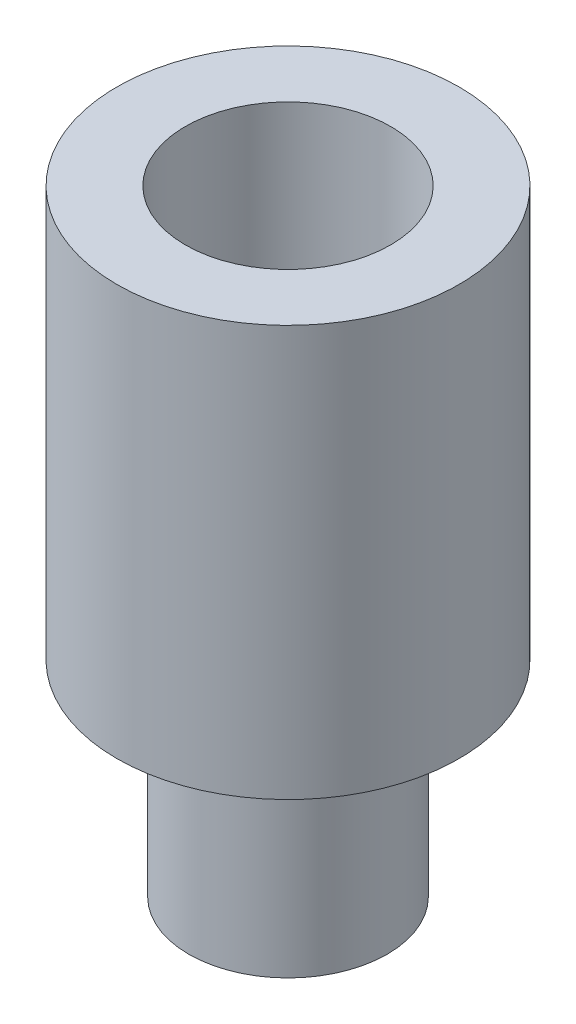
SolidWorks part; units mm, degrees
ref_plane "Front Plane" through (0, 0, 0) normal (0, 0, 1) x (1, 0, 0)
ref_plane "Top Plane" through (0, 0, 0) normal (0, 1, 0) x (1, 0, 0)
ref_plane "Right Plane" through (0, 0, 0) normal (1, 0, 0) x (0, 0, -1)
sketch "Sketch1" plane through (0, 0, 0) normal (0, 1, 0) x (1, 0, 0)
  circle A0 centre (0, 0) radius 7.5
  circle A1 centre (0, 0) radius 12.5
  dimension "D1" = 15
  dimension "D2" = 5
extrude "Boss-Extrude1" add sketch "Sketch1" along normal blind 24
sketch "Sketch2" plane through (0, 0, 0) normal (0, 0, 1) x (1, 0, 0)
  line L0 (0, 0) -> (0, -20)
  line L1 (0, -20) -> (6, -20)
  line L2 (6, -20) -> (6, -8)
  line L3 (6, -8) -> (12.5, 0)
  line L5 (12.5, 0) -> (12.5, 5)
  line L6 (12.5, 0) -> (12.5, 24) construction
  line L7 (12.5, 5) -> (0, 5)
  line L8 (0, 5) -> (0, 0)
  line L9 (-12.5, 0) -> (12.5, 0) construction
  dimension "D1" = 20
  dimension "D2" = 6
  dimension "D3" = 12
  dimension "D4" = 5
revolve "Revolve1" add sketch "Sketch2" angle 360 about L0
sketch "Sketch3" plane through (0, -20, 0) normal (0, -1, 0) x (1, 0, 0)
  circle A0 centre (0, 0) radius 3
  dimension "D1" = 6
extrude "Cut-Extrude1" cut sketch "Sketch3" against normal blind 15
thread "Thread1" pitch 1 method cut profile "Thread Profile2" start angle 0, offset 0, length 20, pitch 1, diameter 6
ref_plane "Plane2" through (3, -20, 0) normal (0, 0, 1) x (1, 0, 0)
sketch "Thread Profile2" plane through (3, -20, 0) normal (0, 0, 1) x (1, 0, 0)
  line L0 (0, 0) -> (0, 1) construction
  line L1 (0, 0) -> (0.5413, 0.3125)
  line L2 (0.5413, 0.3125) -> (0.5413, 0.4375)
  line L3 (0.5413, 0.4375) -> (0, 0.75)
  line L4 (0.5413, 0.375) -> (0, 0.375) construction
  line L11 (0, 0) -> (0, 0.75)
  point P2 (0, 0)
  dimension "Pitch" = 1
  dimension "Profile_Angle" = 60
  dimension "Profile_Land" = 0.125
  dimension "Profile_Height" = 0.5413
sketch "Sketch10" plane through (0, 0, 0) normal (0, 0, 1) x (1, 0, 0)
  line L0 (7.5, 24) -> (-7.5, 24) construction
  circle A0 centre (0, 12.5) radius 3
  dimension "D2" = 6
  dimension "D1" = 11.5
extrude "Cut-Extrude2" [suppressed] cut sketch "Sketch10" against normal through all
sketch "Sketch11" plane through (0, 0, 0) normal (0, 0, 1) x (1, 0, 0)
  line L0 (0, 0) -> (0, -23.6346) construction
  line L1 (6, -8) -> (12.5, -8)
  line L2 (6, -8) -> (6, 0)
  line L3 (6, 0) -> (12.5, 0)
  line L4 (12.5, -8) -> (12.5, 0)
revolve "Cut-Revolve1" cut sketch "Sketch11" angle 360 about L0
sketch "Sketch12" plane through (0, 24, 0) normal (0, 1, 0) x (1, 0, 0)
  circle A0 centre (0, 0) radius 7.5
  circle A1 centre (0, 0) radius 12.5
extrude "Boss-Extrude2" add sketch "Sketch12" along normal blind 6
sketch "Sketch13" plane through (0, 0, 0) normal (0, 0, 1) x (1, 0, 0)
  line L0 (7.5, 30) -> (-7.5, 30) construction
  circle A0 centre (0, 18.5) radius 3
  dimension "D1" = 6
  dimension "D2" = 11.5
extrude "Cut-Extrude3" cut sketch "Sketch13" against normal through all
sketch "Sketch14" plane through (0, 0, 0) normal (0, -1, 0) x (1, 0, 0)
  circle A0 centre (0, 0) radius 6
  circle A1 centre (0, 0) radius 7.25
  dimension "D1" = 14.5
extrude "Boss-Extrude3" add sketch "Sketch14" along normal up to surface (20 mm away) up to face at (3, -20, 0)
sketch "Sketch15" plane through (0, -20, 0) normal (0, -1, 0) x (1, 0, 0)
  circle A1 centre (0, 0) radius 7.25
  circle A2 centre (0, 0) radius 7.25
  dimension "D1" = 0
extrude "Cut-Extrude4" cut sketch "Sketch15" against normal blind 5
